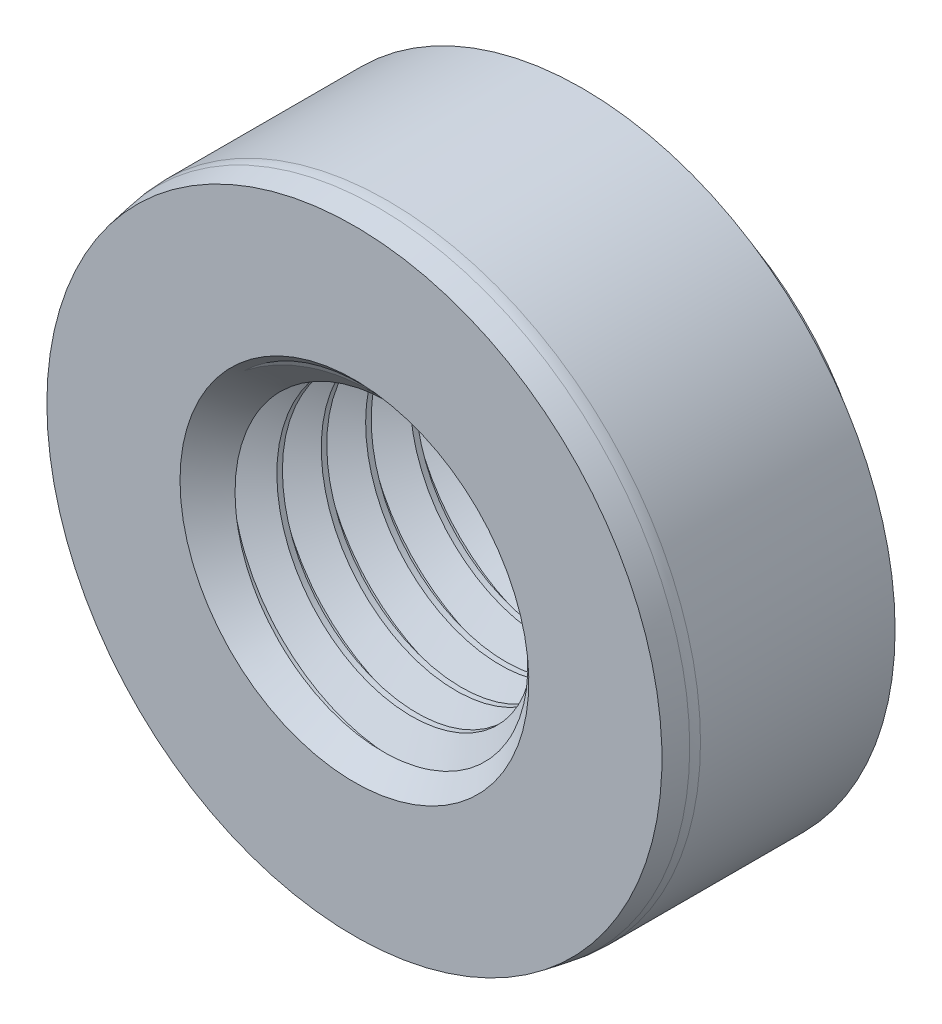
SolidWorks part; units mm, degrees
ref_plane "Front Plane" through (0, 0, 0) normal (0, 0, 1) x (1, 0, 0)
ref_plane "Top Plane" through (0, 0, 0) normal (0, 1, 0) x (1, 0, 0)
ref_plane "Right Plane" through (0, 0, 0) normal (1, 0, 0) x (0, 0, -1)
sketch "Sketch1" plane through (0, 0, 0) normal (1, 0, 0) x (0, 0, -1)
  line L0 (0, -4.365) -> (0, 4.365) construction
  line L1 (0, 4.365) -> (-0.2967, 4.365) construction
  line L2 (-0.6527, 4.2696) -> (-0.6527, 5.1707) construction
  line L3 (-0.6527, 5.1707) -> (-0.89, 5.1707) construction
  line L4 (-0.89, 5.1707) -> (-0.89, 5.59) construction
  line L5 (-0.89, 5.59) -> (-4.97, 5.59) construction
  line L9 (-4.97, 0) -> (0, 0) construction
  line L10 (-4.97, -5.59) -> (-4.97, 5.59) construction
  line L11 (-0.2967, 4.365) -> (-0.6527, 4.2696) construction
  line L12 (-2.485, -3) -> (-2.485, 3) construction
  point P4 (0, 0)
  point P17 (-4.97, 0)
  point P19 (-4.97, 5.59)
  point P20 (-4.97, 0)
  point P24 (-2.485, 0)
  point P26 (-4.97, 0)
  dimension "C" = 8.73
  dimension "A" = 0.89
  dimension "Head OD" = 11.18
  dimension "D9" = 5.1707
  dimension "D10" = 0.2967
  dimension "D11" = 75
  dimension "Thread Size" = 6
  dimension "Head Height" = 4.08
  dimension "D2" = 0.2373
sketch "Sketch2" plane through (0, 0, 0) normal (1, 0, 0) x (0, 0, -1)
  line L0 (0, 0) -> (0, 4.365)
  line L1 (0, -4.365) -> (0, 4.365) construction
  line L2 (0, 4.365) -> (-0.2967, 4.365)
  line L3 (-0.2967, 4.365) -> (-0.6527, 4.2696)
  line L4 (-0.6527, 4.2696) -> (-0.6527, 5.1707)
  line L5 (-0.6527, 5.1707) -> (-0.89, 5.1707)
  line L6 (-0.89, 5.1707) -> (-0.89, 5.59)
  line L7 (-0.89, 5.59) -> (-4.97, 5.59)
  line L10 (-4.97, 0) -> (0, 0)
  line L12 (-4.97, 5.59) -> (-4.97, 0)
revolve "Revolve1" add sketch "Sketch2" angle 360 about L9
sketch "Sketch5" plane through (0, 0, 0.6527) normal (0, 0, -1) x (-1, 0, 0)
  line L0 (0, 0) -> (-5.1707, 0) construction
  line L1 (-5.1191, -0.7289) -> (-4.6537, 0)
  line L2 (-4.6537, 0) -> (-5.1191, 0.7289)
  circle A0 centre (0, 0) radius 5.1707 construction
  arc A1 (-5.1191, 0.7289) -> (-5.1191, -0.7289) centre (0, 0) ccw
  point P6 (-5.1707, 0)
  dimension "D2" = 4.6537
  dimension "D1" = 1.4627
extrude "Cut-Extrude2" cut sketch "Sketch5" against normal up to surface (0.2373 mm away) up to face at (5.59, 0, 0.89)
fillet "Fillet3" radius 0.2194 1 edges at (4.6537, 0, 0.7713)
pattern_circular "CirPattern1" count 24 over 360 about axis through (0, 0, 0) along (0, 0, 1) of "Cut-Extrude2", "Fillet3"
fillet "Fillet4" radius 0.2194 24 edges at (4.0656, 3.1197, 0.7713) (3.1197, 4.0656, 0.7713) (1.9611, 4.7345, 0.7713) (0.6689, 5.0808, 0.7713) (-1.9611, 4.7345, 0.7713) (-0.6689, 5.0808, 0.7713) (-3.1197, 4.0656, 0.7713) (-4.0656, 3.1197, 0.7713) (-4.7345, 1.9611, 0.7713) (-5.0808, 0.6689, 0.7713) (-4.7345, -1.9611, 0.7713) (-5.0808, -0.6689, 0.7713) (-4.0656, -3.1197, 0.7713) (-3.1197, -4.0656, 0.7713) (-1.9611, -4.7345, 0.7713) (-0.6689, -5.0808, 0.7713) (0.6689, -5.0808, 0.7713) (1.9611, -4.7345, 0.7713) (3.1197, -4.0656, 0.7713) (4.0656, -3.1197, 0.7713) (4.7345, -1.9611, 0.7713) (5.0808, -0.6689, 0.7713) (4.7345, 1.9611, 0.7713) (5.0808, 0.6689, 0.7713)
sketch "Sketch11" plane through (0, 0, 0) normal (0, 1, 0) x (1, 0, 0)
  line L0 (4.6537, -0.6527) -> (5.1707, -0.8409)
  line L2 (5.1707, -0.8409) -> (5.1707, -0.6527)
  line L3 (0, -0.6527) -> (5.1707, -0.6527) construction
  line L4 (4.6537, -0.6527) -> (5.1707, -0.6527)
  line L5 (0, -4.97) -> (0, 0) construction
  dimension "D2" = 4.6537
  dimension "D1" = 20
revolve "Cut-Revolve3" cut sketch "Sketch11" angle 360 about L9
sketch "Sketch12" plane through (0, 0, 0) normal (1, 0, 0) x (0, 0, -1)
  line L0 (-4.97, 0) -> (0, 0)
  line L1 (0, 0) -> (0, -3)
  line L2 (0, -4.365) -> (0, 4.365) construction
  line L3 (0, -3) -> (-4.97, -3)
  line L5 (-4.97, -3) -> (-4.97, 0)
revolve "Cut-Revolve4" cut sketch "Sketch12" angle 360 about L9
chamfer "Chamfer1" distance 0.51 angle 10 1 edges at (5.59, 0, 4.97)
fillet "Fillet5" radius 1.02 2 edges at (-5.59, 0, 4.46) (4.365, 0, 0.2967)
sketch "Sketch17" plane through (0, 0, 4.97) normal (0, 0, 1) x (1, 0, 0)
  line L0 (0, 3) -> (0, -3) construction
  line L1 (0, 0) -> (-2.1213, -2.1213) construction
  circle A0 centre (0, 0) radius 3 construction
  point P8 (-2.1213, -2.1213)
  dimension "D1" = 45
sketch "Sketch13" plane through (0, 0, 0) normal (0, 0, -1) x (-1, 0, 0)
  circle A0 centre (0, 0) radius 3 construction
  circle A1 centre (0, 0) radius 3
curve "Helix/Spiral1" pitch 0.7937 height 5.7637 turns 7.2614 parameters "Thread Pitch"=0.7937
sketch "Sketch14" plane through (0, 0, 0) normal (1, 0, 0) x (0, 0, -1)
  line L0 (-0.0496, 3.0859) -> (0.7441, 3.0859) construction
  line L1 (-0.0496, 3.0859) -> (0.3473, 2.3985) construction
  line L2 (0.3473, 2.3985) -> (0.7441, 3.0859) construction
  line L3 (0.3473, 3.0859) -> (0.3473, 3) construction
  line L4 (0.3473, 2.3985) -> (0.3473, 2.4844) construction
  line L5 (0.2977, 2.4844) -> (0.3969, 2.4844) construction
  line L6 (0, 3) -> (0.6945, 3) construction
  line L7 (-0.0248, 3.043) -> (0.7193, 3.043) construction
  line L8 (-0.0248, 3.043) -> (0.7193, 3.043)
  line L9 (0.7193, 3.043) -> (0.3969, 2.4844)
  line L10 (0.3969, 2.4844) -> (0.2977, 2.4844)
  line L11 (0.2977, 2.4844) -> (-0.0248, 3.043)
  point P12 (0.3473, 3.043)
  dimension "D1" = 0.7937
  dimension "D2" = 0.0992
sweep "Sweep1" add profiles "Sketch14" path "Helix/Spiral1"
sketch "Sketch15" plane through (0, 0, 0) normal (0, 0, -1) x (-1, 0, 0)
  circle A2 centre (0, 0) radius 3.1191
  circle A3 centre (0, 0) radius 3.1191
  dimension "D1" = 0.1191
extrude "Cut-Extrude3" cut sketch "Sketch15" against normal through all draft 47 and the other way through all draft 47
sketch "Sketch16" plane through (0, 0, 4.97) normal (0, 0, 1) x (1, 0, 0)
  circle A1 centre (0, 0) radius 3.1191
  circle A2 centre (0, 0) radius 3.1191
  dimension "D1" = 0
extrude "Cut-Extrude4" cut sketch "Sketch16" against normal through all draft 47 and the other way through all draft 47
equation "\"D9@Sketch1\"=\"Head OD@Sketch1\" / 2 * .925"
equation "\"D10@Sketch1\"=\"A@Sketch1\" / 3"
equation "\"D1@Sketch5\" =  ( \"Head OD@Sketch1\" * 3.14 )  / 24"
equation "\"D2@Sketch5\"=\"D9@Sketch1\"*.9"
equation "\"D1@Fillet3\"=\"D1@Sketch5\"*.15"
equation "\"D1@Fillet4\"=\"D1@Fillet3\""
equation "\"D2@Sketch1\"=\"A@Sketch1\"/3.75"
equation "\"D1@Chamfer1\"=\"Head Height@Sketch1\"/8"
equation "\"D1@Fillet5\"=\"D1@Chamfer1\"*2"
equation "\"D2@Sketch11\"=\"D9@Sketch1\"*.9"
equation "\"D3@Helix/Spiral1\" = \"Thread Pitch@Helix/Spiral1\" + \"Head Height@Sketch1\" + \"A@Sketch1\""
equation "\"D2@Sketch14\"=\"D1@Sketch14\"/8"
equation "\"D1@Sketch14\" = \"Thread Pitch@Helix/Spiral1\""
equation "\"D1@Sketch15\"=\"Thread Pitch@Helix/Spiral1\"*.15"
